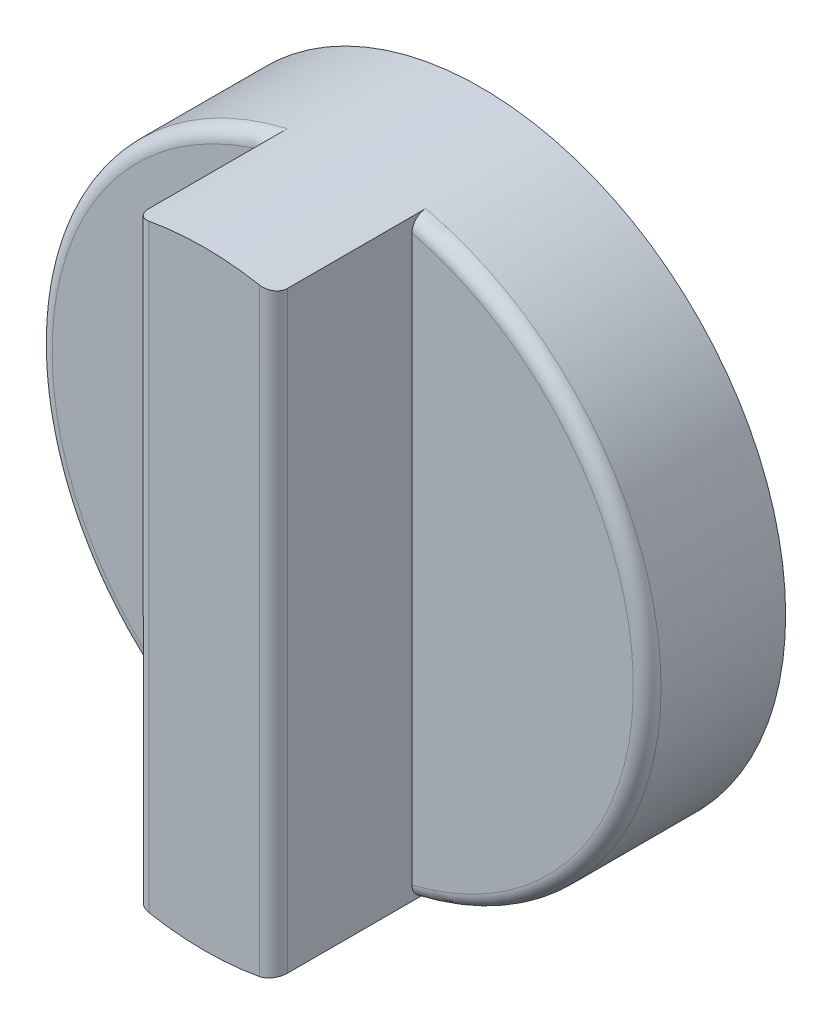
SolidWorks part; units mm, degrees
ref_plane "Plan de face" through (0, 0, 0) normal (0, 0, 1) x (1, 0, 0)
ref_plane "Plan de dessus" through (0, 0, 0) normal (0, 1, 0) x (1, 0, 0)
ref_plane "Plan de droite" through (0, 0, 0) normal (1, 0, 0) x (0, 0, -1)
sketch "Esquisse1" plane through (0, 0, 0) normal (0, 0, 1) x (1, 0, 0)
  circle A0 centre (0, 0) radius 11
  dimension "D1" = 22
extrude "Boss.-Extru.1" add sketch "Esquisse1" along normal blind 5
sketch "Esquisse2" plane through (0, 0, 5) normal (0, 0, 1) x (1, 0, 0)
  line L0 (0, 5.7045) -> (0, -6.8994) construction
  line L2 (-2.5, 10.7121) -> (-2.5, -10.7121)
  line L4 (2.5, 10.7121) -> (2.5, -10.7121)
  circle A0 centre (0, 0) radius 11 construction
  arc A1 (-2.5, -10.7121) -> (2.5, -10.7121) centre (0, 0) ccw
  arc A2 (2.5, 10.7121) -> (-2.5, 10.7121) centre (0, 0) ccw
  dimension "D1" = 5
extrude "Boss.-Extru.2" add sketch "Esquisse2" along normal blind 5
fillet "Congé1" radius 0.5 2 edges
fillet "Congé2" radius 0.5 2 edges at (-2.5, 0, 10) (2.5, 0, 10)
